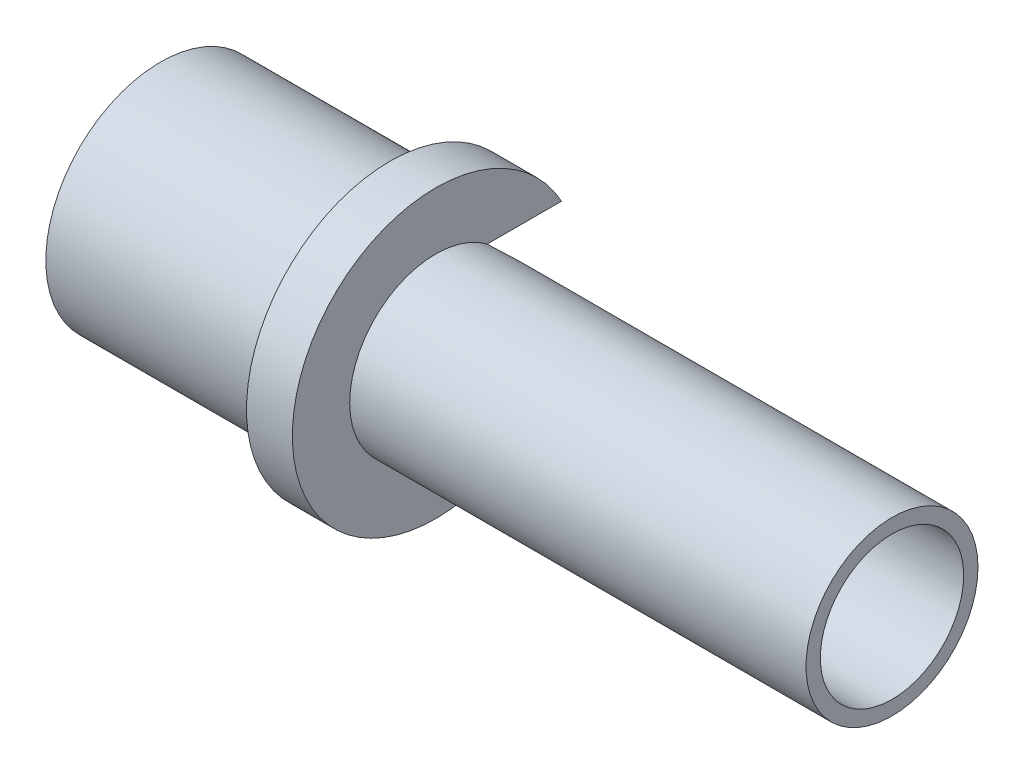
SolidWorks part; units mm, degrees
material "6061-T6 (SS)"
ref_plane "Front Plane" through (0, 0, 0) normal (0, 0, 1) x (1, 0, 0)
ref_plane "Top Plane" through (0, 0, 0) normal (0, 1, 0) x (1, 0, 0)
ref_plane "Right Plane" through (0, 0, 0) normal (1, 0, 0) x (0, 0, -1)
sketch "Sketch1" plane through (0, 0, 0) normal (0, 0, 1) x (1, 0, 0)
  line L0 (0, 0) -> (-16.6687, 0) construction
  line L1 (2.41, 3.9687) -> (2.41, 4.7625)
  line L2 (2.41, 4.7625) -> (-22.86, 4.7625)
  line L3 (-22.86, 4.7625) -> (-22.86, 7.9375)
  line L4 (-22.86, 7.9375) -> (-25.4, 7.9375)
  line L5 (-25.4, 7.9375) -> (-25.4, 6.35)
  line L6 (-25.4, 6.35) -> (-38.1, 6.35)
  line L7 (-38.1, 6.35) -> (-38.1, 3.9687)
  line L8 (-38.1, 3.9687) -> (2.41, 3.9687)
  line L9 (-25.4, -15.5875) -> (-25.4, 15.5875) construction
  line L13 (1.14, -6) -> (1.14, 6) construction
  point P9 (-2.7157, 4.7625)
  point P14 (24.9911, 3.9687)
  dimension "D1" = 7.9375
  dimension "D4" = 12.7
  dimension "D3" = 9.525
  dimension "D2" = 2.54
  dimension "D5" = 1.5875
  dimension "D6" = 12.7
  dimension "D7" = 1.27
revolve "Revolve1" add sketch "Sketch1" angle 360 about L0
sketch "Sketch2" plane through (2.41, 0, 0) normal (1, 0, 0) x (0, 0, -1)
  line L0 (1.3441, 3.7342) -> (7.0042, 3.7342)
  line L1 (7.0042, -3.7342) -> (1.3441, -3.7342)
  line L2 (0, 0) -> (14.3216, 0) construction
  circle A0 centre (0, 0) radius 3.9687 construction
  circle A1 centre (0, 0) radius 7.9375 construction
  arc A2 (1.3441, 3.7342) -> (1.3441, -3.7342) centre (0, 0) cw
  arc A3 (7.0042, 3.7342) -> (7.0042, -3.7342) centre (0, 0) cw
  arc A4 (3.6742, 3.7342) -> (3.6742, -3.7342) centre (0, 0) cw construction
  circle A5 centre (5.2387, 0) radius 1.27 construction
  circle A6 centre (4.623, 2.4642) radius 1.27 construction
  circle A7 centre (4.623, -2.4642) radius 1.27 construction
  dimension "D1" = 1.27
  dimension "D2" = 2.54
extrude "Cut-Extrude1" [suppressed] cut sketch "Sketch2" against normal through all both
sketch "Sketch3" plane through (0, 0, 0) normal (0, 0, 1) x (1, 0, 0)
  line L0 (-38.1, 3.81) -> (-38.1, -3.81)
  line L1 (-38.1, 6.35) -> (-38.1, -6.35) construction
  line L2 (-38.1, -3.81) -> (-22.86, -3.81)
  line L4 (-22.86, 3.81) -> (-38.1, 3.81)
  line L5 (-19.685, -0.635) -> (-19.685, 0.635)
  line L6 (-19.685, 0) -> (0, 0) construction
  line L8 (-22.86, -7.9375) -> (-22.86, 7.9375) construction
  arc A1 (-22.86, -3.81) -> (-19.685, -0.635) centre (-22.86, -0.635) ccw
  arc A2 (-19.685, 0.635) -> (-22.86, 3.81) centre (-22.86, 0.635) ccw
  point P6 (-25.4, -3.81)
  point P7 (-22.86, -3.81)
  dimension "D1" = 7.62
  dimension "D2" = 3.175
extrude "Cut-Extrude2" cut sketch "Sketch3" against normal up to next
equation "\"bearing1\"=0.273438"
equation "\"D1@Sketch1\"=5/16"
